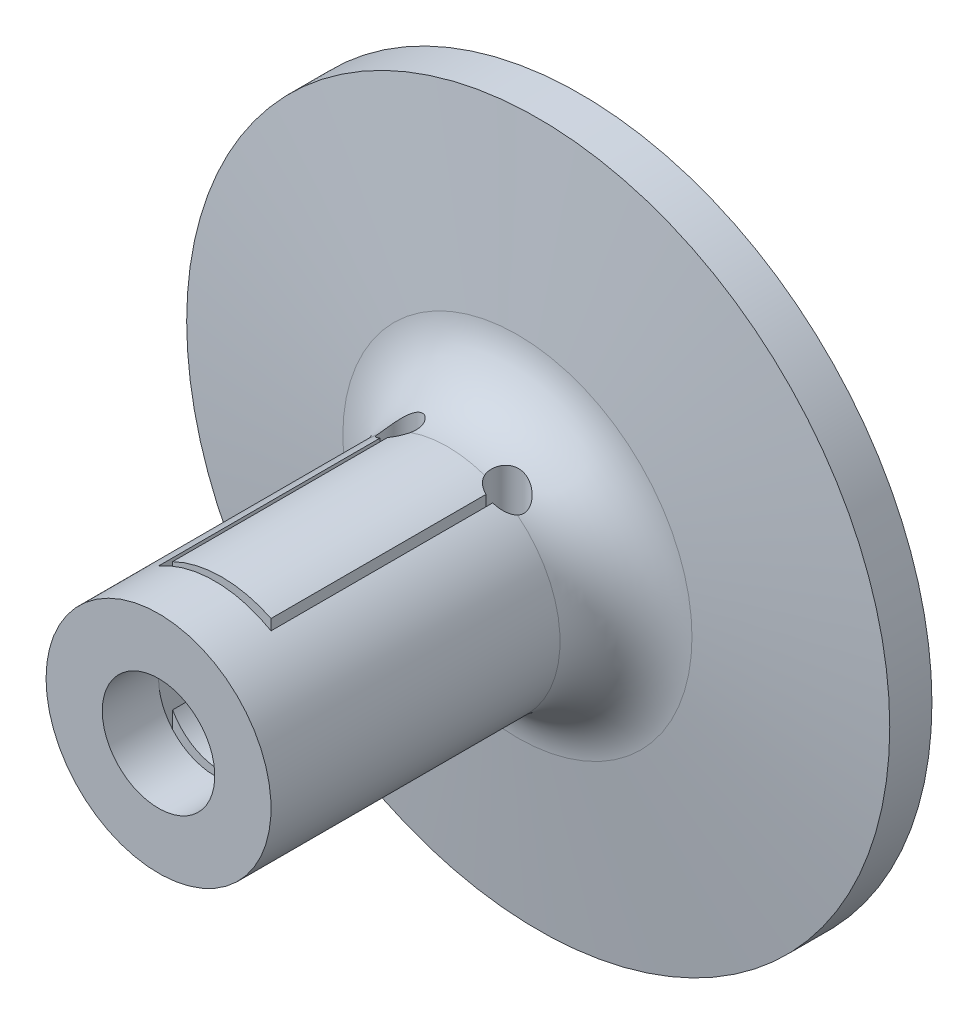
SolidWorks part; units mm, degrees
material "ABS"
ref_plane "xy" through (0, 0, 0) normal (0, 0, 1) x (1, 0, 0)
ref_plane "xz" through (0, 0, 0) normal (0, 1, 0) x (1, 0, 0)
ref_plane "yz" through (0, 0, 0) normal (1, 0, 0) x (0, 0, -1)
ref_axis "x" through (-27.5, 0, 0) along (1, 0, 0)
ref_axis "y" through (0, 27.5, 0) along (0, -1, 0)
ref_axis "z" through (0, 0, -1.5) along (0, 0, 1)
sketch "Skizze1" plane through (0, 0, 0) normal (0, 1, 0) x (1, 0, 0)
  line L0 (0, 0) -> (0, -30) construction
  line L1 (0, 0) -> (25, 0)
  line L2 (25, 0) -> (25, -3)
  line L3 (25, -3) -> (8, -5)
  line L4 (8, -5) -> (8, -30)
  line L5 (8, -30) -> (4, -30)
  line L6 (4, -30) -> (4, -3)
  line L7 (4, -3) -> (0, -3)
  line L8 (0, -3) -> (0, 0)
  dimension "D1" = 50
  dimension "D2" = 8
  dimension "D3" = 4
  dimension "D4" = 3
  dimension "D5" = 30
  dimension "D6" = 5
revolve "Rotation1" add sketch "Skizze1" angle 360 about L0
sketch "Skizze2" plane through (0, 0, 0) normal (0, 1, 0) x (1, 0, 0)
  line L1 (-4, -26) -> (4, -26)
  line L2 (-4, -26) -> (-4, -9)
  line L3 (-4, -9) -> (4, -9) construction
  line L4 (4, -26) -> (4, -9)
  point P4 (0, -9)
  dimension "D1" = 4
  dimension "D2" = 4
  dimension "D3" = 8
extrude "Schnitt-Linear-Austragen-Dünn1" cut sketch "Skizze2" against normal through all and the other way through all thin thin type one direction wall 0.5
sketch "Skizze4" plane through (0, 0, 0) normal (0, 1, 0) x (1, 0, 0)
  line L0 (-4, -9) -> (4, -9) construction
  circle A0 centre (-3.8, -9) radius 1.25
  dimension "D2" = 2.5
  dimension "D1" = 0.2
extrude "Schnitt-Linear austragen1" cut sketch "Skizze4" against normal through all and the other way through all
mirror "Spiegeln1" about plane through (0, 0, 0) normal (1, 0, 0) of "Schnitt-Linear austragen1"
fillet "Verrundung1" radius 5 1 edges at (-8, 0, 5)
